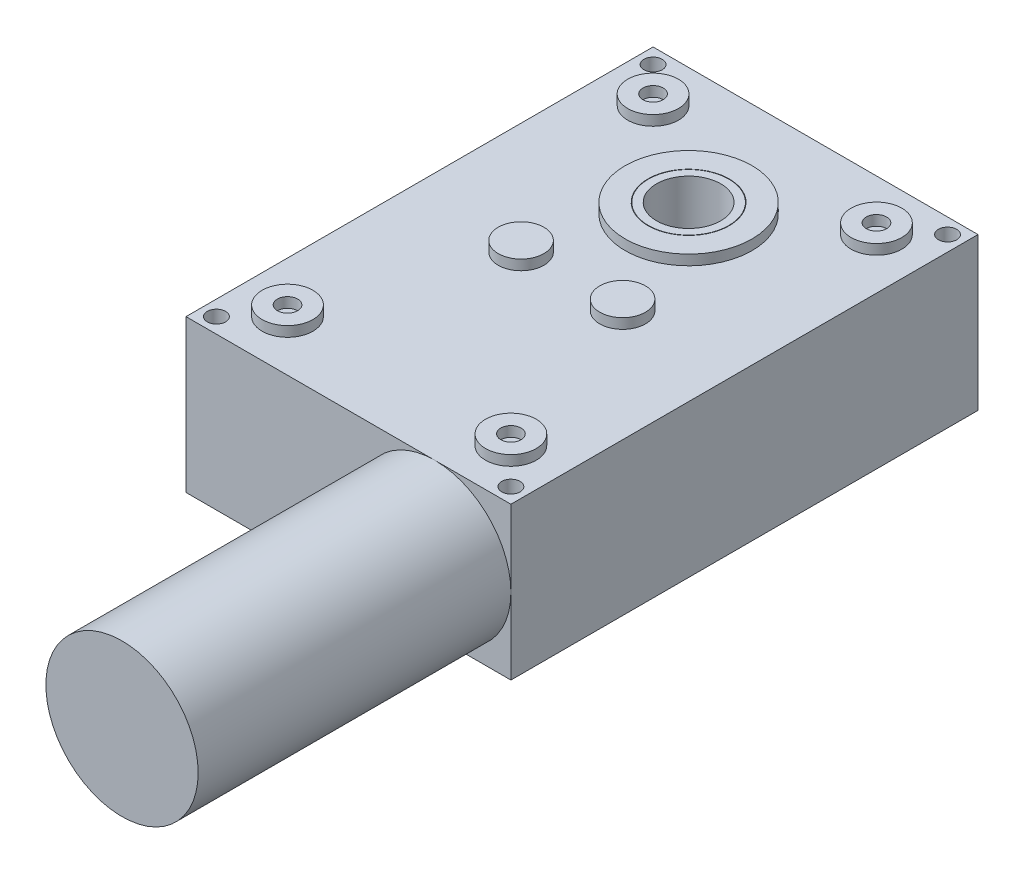
SolidWorks part; units mm, degrees
ref_plane "Alzado" through (0, 0, 0) normal (0, 0, 1) x (1, 0, 0)
ref_plane "Planta" through (0, 0, 0) normal (0, 1, 0) x (1, 0, 0)
ref_plane "Vista lateral" through (0, 0, 0) normal (1, 0, 0) x (0, 0, -1)
sketch "Croquis1" plane through (0, 0, 0) normal (0, 1, 0) x (1, 0, 0)
  line L1 (-16, -23) -> (16, -23)
  line L2 (-16, -23) -> (-16, 23)
  line L3 (-16, 23) -> (16, 23)
  line L4 (16, -23) -> (16, 23)
  line L5 (-16, -23) -> (16, 23) construction
  line L6 (-16, 23) -> (16, -23) construction
  point P0 (0, 0)
  dimension "D1" = 46
  dimension "D2" = 32
extrude "Saliente-Extruir1" add sketch "Croquis1" along normal blind 15
sketch "Croquis2" plane through (0, 0, 23) normal (0, 0, 1) x (1, 0, 0)
  line L0 (-16, 15) -> (-16, 0) construction
  line L1 (16, 15) -> (16, 0) construction
  circle A0 centre (8.5, 7.5) radius 7.5
  point P4 (-16, 7.5)
  dimension "D1" = 15
extrude "Saliente-Extruir2" add sketch "Croquis2" along normal blind 30.8
sketch "Croquis3" plane through (0, 15, 0) normal (0, 1, 0) x (1, 0, 0)
  line L0 (0, -8.25) -> (0, 8.25) construction
  line L1 (16, 23) -> (-16, 23) construction
  line L2 (-8.25, 0) -> (8.25, 0) construction
  line L3 (-16, 23) -> (-16, -23) construction
  circle A0 centre (0, 10.5) radius 6.25
  circle A1 centre (-11, 18) radius 2.5
  circle A3 centre (-5, -1) radius 2.25
  circle A5 centre (-11, 18) radius 1
  circle A6 centre (11, 18) radius 1
  circle A7 centre (11, 18) radius 2.5
  circle A8 centre (11, -18) radius 1
  circle A9 centre (11, -18) radius 2.5
  circle A10 centre (-11, -18) radius 1
  circle A11 centre (-11, -18) radius 2.5
  circle A12 centre (0, 10.5) radius 4
  circle A13 centre (5, -1) radius 2.25
  circle A14 centre (0, 10.5) radius 3.9587
  circle A15 centre (0, 10.5) radius 3.1638
  circle A16 centre (-14.5, 21.5) radius 0.75
  circle A17 centre (-14.5, -21.5) radius 0.75
  circle A18 centre (14.5, 21.5) radius 0.75
  circle A19 centre (14.5, -21.5) radius 0.75
  dimension "D1" = 5
  dimension "D2" = 12.5
  dimension "D3" = 4.5
  dimension "D7" = 2
  dimension "D8" = 8
  dimension "D11" = 1.5
  dimension "D4" = 12.5
  dimension "D5" = 5
  dimension "D6" = 5
  dimension "D9" = 5
  dimension "D10" = 11.5
  dimension "D12" = 1.5
  dimension "D13" = 1.5
extrude "Saliente-Extruir3" add sketch "Croquis3" along normal blind 1 contours A1 A5 | A7 A6 | A3 | A13 | A11 A10 | A9 A8 | A0 A12 | A14 A15 region at (-6.0732, 15, -10.5) region at (-13.4293, 15, -18) region at (-5, 15, 1) region at (8.5707, 15, -18) region at (8.5707, 15, 18) region at (-13.4293, 15, 18) region at (5, 15, 1) region at (-3.8467, 15, -10.5)
extrude "Cortar-Extruir1" cut sketch "Croquis3<3>" against normal blind 10 contours A15 region at (0, 15, -10.5)
sketch "Croquis3<3>" plane through (0, 15, 0) normal (0, 1, 0) x (1, 0, 0) same geometry as "Croquis3"
hole_wizard "Taladro de margen para M1.41" positions "Croquis4" profile "Croquis5" hole size "M1.4" standard "ISO"
sketch "Croquis4" plane through (0, 15, 0) normal (0, 1, 0) x (1, 0, 0)
  point P0 (-14.5, 21.5)
  point P3 (14.5, 21.5)
  point P6 (-14.5, -21.5)
  point P9 (14.5, -21.5)
sketch "Croquis5" plane through (-14.5, 15, -21.5) normal (1, 0, 0) x (0, 0, 1)
  line L0 (0, 0) -> (0, 3.5408)
  line L1 (0, 3.5408) -> (0.9, 3)
  line L2 (0.9, 3) -> (0.9, 0)
  line L5 (0.9, 0) -> (0, 0)
  line L10 (0, 3.5408) -> (-0.9, 3) construction
  line L11 (0, -6.35) -> (0, 107.95) construction
  dimension "Diámetro de taladro" = 1.8
  dimension "Profundidad de taladro" = 3
  dimension "Ángulo de perforador" = 118
